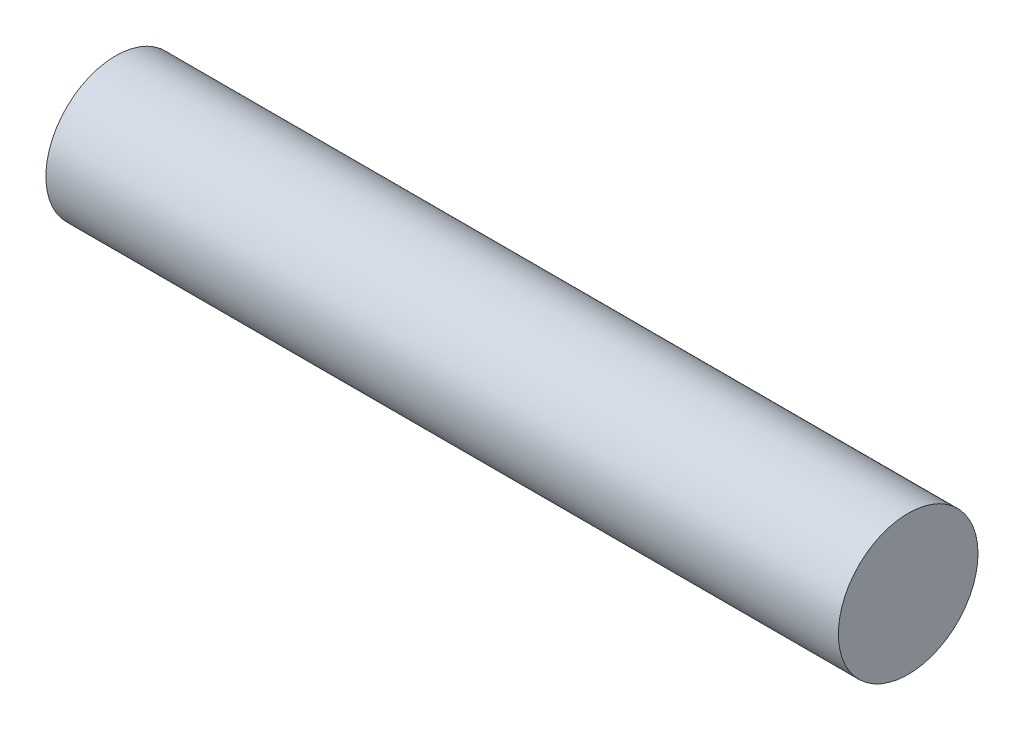
SolidWorks part; units mm, degrees
ref_plane "Front Plane" through (0, 0, 0) normal (0, 0, 1) x (1, 0, 0)
ref_plane "Top Plane" through (0, 0, 0) normal (0, 1, 0) x (1, 0, 0)
ref_plane "Right Plane" through (0, 0, 0) normal (1, 0, 0) x (0, 0, -1)
sketch "Sketch1" plane through (0, 0, 0) normal (1, 0, 0) x (0, 0, -1)
  circle A0 centre (0, 0) radius 13.9352
  dimension "D1" = 27.8704
extrude "Boss-Extrude1" add sketch "Sketch1" against normal blind 79.0745 and the other way blind 79.0745
